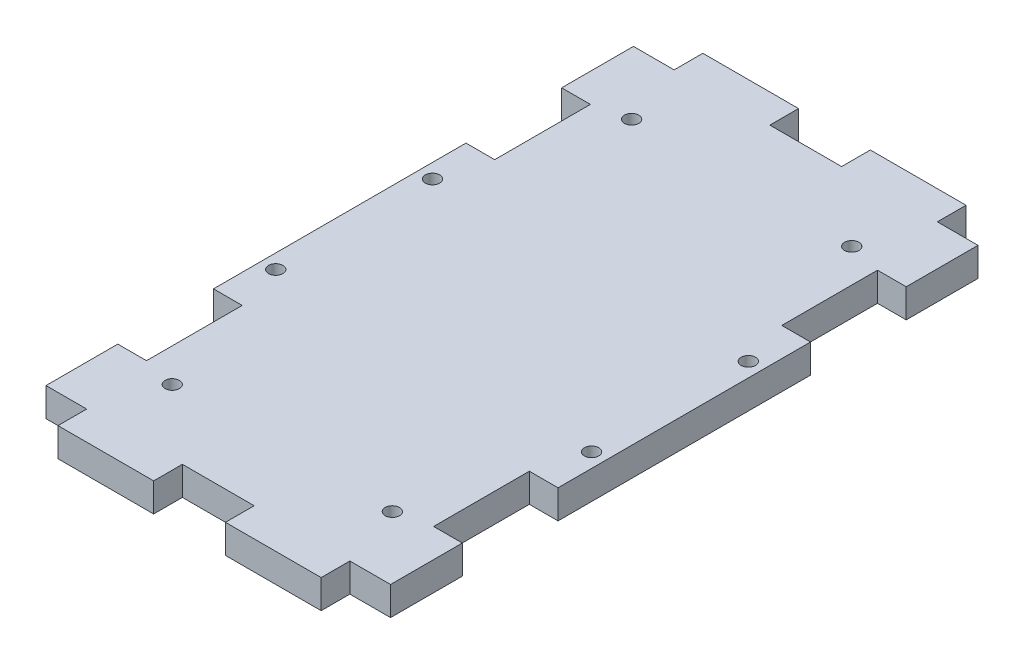
SolidWorks part; units mm, degrees
ref_plane "Plan de face" through (0, 0, 0) normal (0, 0, 1) x (1, 0, 0)
ref_plane "Plan de dessus" through (0, 0, 0) normal (0, 1, 0) x (1, 0, 0)
ref_plane "Plan de droite" through (0, 0, 0) normal (1, 0, 0) x (0, 0, -1)
sketch "Esquisse1" plane through (0, 0, 0) normal (0, 1, 0) x (1, 0, 0)
  line L0 (0, 89.2093) -> (0, -94.1785) construction
  line L1 (-36, 61.38) -> (36, 61.38)
  line L2 (-36, 61.38) -> (-36, -61.38)
  line L3 (-36, -61.38) -> (36, -61.38)
  line L4 (36, 61.38) -> (36, -61.38)
  dimension "D1" = 72
  dimension "D2" = 122.76
  dimension "D3" = 61.38
  dimension "D4" = 36
extrude "Boss.-Extru.1" add sketch "Esquisse1" along normal blind 6
sketch "Esquisse2" plane through (0, 6, 0) normal (0, 1, 0) x (1, 0, 0)
  line L0 (36, 61.38) -> (-36, 61.38) construction
  line L1 (-27.5, 61.38) -> (-7.5, 61.38)
  line L2 (-27.5, 61.38) -> (-27.5, 67.38)
  line L3 (-27.5, 67.38) -> (-7.5, 67.38)
  line L4 (-7.5, 61.38) -> (-7.5, 67.38)
  line L5 (-36, 61.38) -> (-36, -61.38) construction
  line L6 (7.5, 61.38) -> (27.5, 61.38)
  line L7 (7.5, 61.38) -> (7.5, 67.38)
  line L8 (7.5, 67.38) -> (27.5, 67.38)
  line L9 (27.5, 61.38) -> (27.5, 67.38)
  line L12 (-114.0924, 0) -> (165.6917, 0) construction
  line L13 (27.5, -61.38) -> (27.5, -67.38)
  line L14 (7.5, -67.38) -> (27.5, -67.38)
  line L15 (7.5, -61.38) -> (7.5, -67.38)
  line L16 (7.5, -61.38) -> (27.5, -61.38)
  line L17 (-7.5, -61.38) -> (-7.5, -67.38)
  line L18 (-27.5, -67.38) -> (-7.5, -67.38)
  line L19 (-27.5, -61.38) -> (-27.5, -67.38)
  line L20 (-27.5, -61.38) -> (-7.5, -61.38)
  dimension "D1" = 6
  dimension "D2" = 20
  dimension "D3" = 6
  dimension "D4" = 20
  dimension "D5" = 15
  dimension "D6" = 8.5
extrude "Boss.-Extru.2" add sketch "Esquisse2" against normal blind 6
sketch "Esquisse3" plane through (0, 6, 0) normal (0, 1, 0) x (1, 0, 0)
  line L0 (-36, 61.38) -> (-36, -61.38) construction
  line L1 (-36, 46.38) -> (-30, 46.38)
  line L2 (-36, 46.38) -> (-36, 26.38)
  line L3 (-36, 26.38) -> (-30, 26.38)
  line L4 (-30, 46.38) -> (-30, 26.38)
  line L5 (0, 89.8506) -> (0, -95.1082) construction
  line L6 (-36, -26.38) -> (-30, -26.38)
  line L7 (-36, -26.38) -> (-36, -46.38)
  line L8 (-36, -46.38) -> (-30, -46.38)
  line L9 (-30, -26.38) -> (-30, -46.38)
  line L10 (-36, -61.38) -> (-27.5, -61.38) construction
  line L11 (-27.5, 61.38) -> (-36, 61.38) construction
  line L12 (30, -26.38) -> (30, -46.38)
  line L13 (36, -46.38) -> (30, -46.38)
  line L14 (36, -26.38) -> (36, -46.38)
  line L15 (36, -26.38) -> (30, -26.38)
  line L16 (30, 46.38) -> (30, 26.38)
  line L17 (36, 26.38) -> (30, 26.38)
  line L18 (36, 46.38) -> (36, 26.38)
  line L19 (36, 46.38) -> (30, 46.38)
  dimension "D1" = 6
  dimension "D2" = 20
  dimension "D3" = 20
  dimension "D4" = 6
  dimension "D5" = 15
  dimension "D6" = 15
extrude "Enlèv. mat.-Extru.1" cut sketch "Esquisse3" against normal blind 6
sketch "Esquisse4" plane through (0, 6, 0) normal (0, 1, 0) x (1, 0, 0)
  line L0 (0, 97.8129) -> (0, -122.6259) construction
  line L1 (-33, 63.4421) -> (-33, -96.2021) construction
  line L2 (-36, 26.38) -> (-30, 26.38) construction
  line L3 (-30, -26.38) -> (-36, -26.38) construction
  line L4 (-36, 26.38) -> (-36, -26.38) construction
  line L5 (23, 50.212) -> (23, -22.9184) construction
  line L6 (30, 46.38) -> (30, 26.38) construction
  line L7 (36, 61.38) -> (27.5, 61.38) construction
  circle A0 centre (-33, 16.38) radius 1.5
  circle A1 centre (-33, -16.38) radius 1.5
  circle A2 centre (33, -16.38) radius 1.5
  circle A3 centre (33, 16.38) radius 1.5
  circle A4 centre (23, 48) radius 1.5
  circle A5 centre (23, -48) radius 1.5
  circle A6 centre (-23, -48) radius 1.5
  circle A7 centre (-23, 48) radius 1.5
  point P27 (31.75, 61.38)
  dimension "D1" = 3
  dimension "D2" = 10
  dimension "D3" = 3
  dimension "D4" = 10
  dimension "D7" = 3
  dimension "D8" = 13.38
  dimension "D9" = 3
  dimension "D10" = 96
  dimension "D5" = 3
  dimension "D6" = 7
extrude "Enlèv. mat.-Extru.2" cut sketch "Esquisse4" against normal blind 6
equation "\"D3@Esquisse1\"=\"D2@Esquisse1\"/2"
equation "\"D4@Esquisse1\"=\"D1@Esquisse1\"/2"
